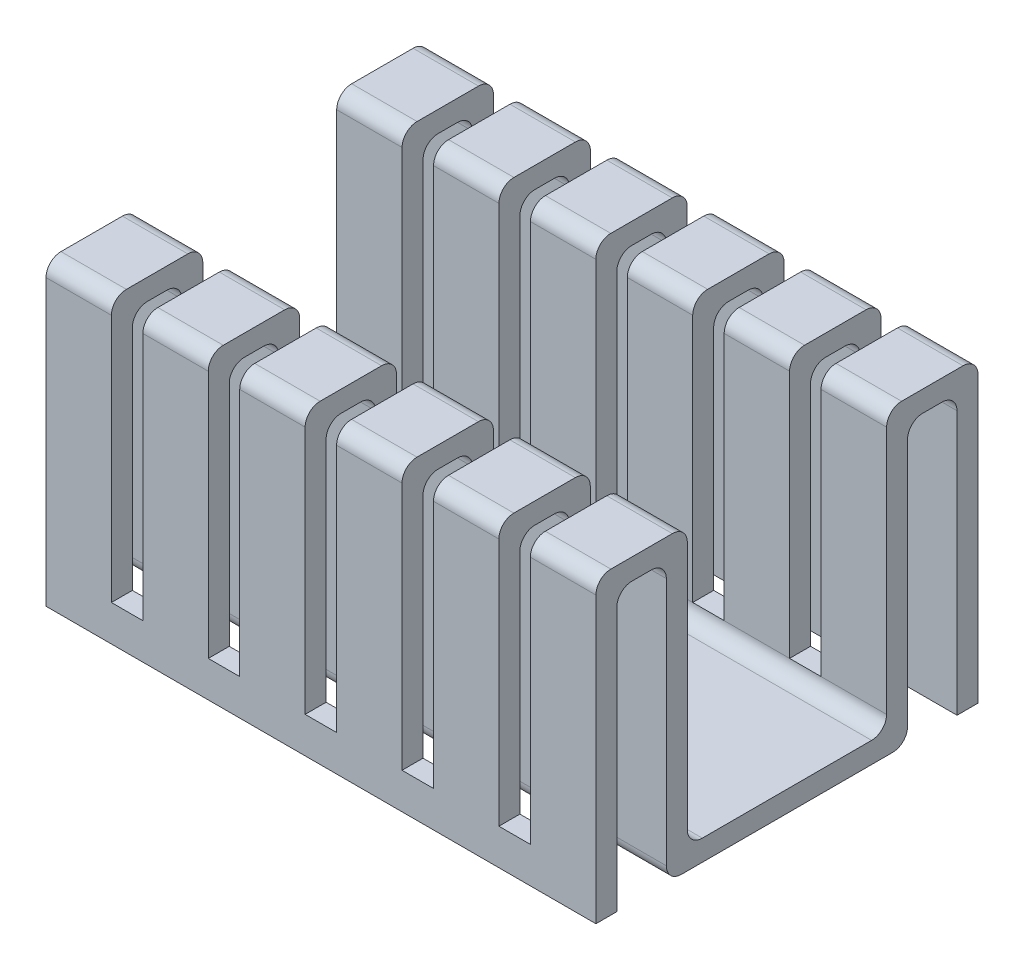
SolidWorks part; units mm, degrees
ref_plane "Front Plane" through (0, 0, 0) normal (0, 0, 1) x (1, 0, 0)
ref_plane "Top Plane" through (0, 0, 0) normal (0, 1, 0) x (1, 0, 0)
ref_plane "Right Plane" through (0, 0, 0) normal (1, 0, 0) x (0, 0, -1)
sketch "Croquis1" plane through (0, 0, 0) normal (1, 0, 0) x (0, 0, -1)
  line L5 (0, 0) -> (0, 19)
  line L9 (-1, 20) -> (-5.1, 20)
  line L10 (0, 0) -> (-1.4, 0)
  line L11 (-1.4, 0) -> (-1.4, 17.6)
  line L12 (-3.7, 18.6) -> (-2.4, 18.6)
  line L13 (-4.7, 17.6) -> (-4.7, 1)
  line L14 (-5.7, 0) -> (-19.8, 0)
  line L15 (-6.1, 2.4) -> (-6.1, 19)
  line L16 (-7.1, 1.4) -> (-18.4, 1.4)
  line L17 (-6.1, 9.3) -> (-4.7, 9.3) construction
  line L18 (-6.1, 1.4) -> (-6.1, 0) construction
  line L19 (-3.05, 20) -> (-3.05, 18.6) construction
  line L20 (-12.75, 22.5984) -> (-12.75, -4.8064) construction
  line L21 (-22.45, 20) -> (-22.45, 18.6) construction
  line L22 (-19.4, 1.4) -> (-19.4, 0) construction
  line L23 (-19.4, 9.3) -> (-20.8, 9.3) construction
  line L24 (-19.4, 2.4) -> (-19.4, 19)
  line L25 (-20.8, 17.6) -> (-20.8, 1)
  line L26 (-21.8, 18.6) -> (-23.1, 18.6)
  line L27 (-24.1, 0) -> (-24.1, 17.6)
  line L28 (-25.5, 0) -> (-24.1, 0)
  line L29 (-24.5, 20) -> (-20.4, 20)
  line L30 (-25.5, 0) -> (-25.5, 19)
  arc A0 (-20.8, 1) -> (-19.8, 0) centre (-19.8, 1) ccw
  arc A1 (-18.4, 1.4) -> (-19.4, 2.4) centre (-18.4, 2.4) cw
  arc A2 (-4.7, 1) -> (-5.7, 0) centre (-5.7, 1) cw
  arc A3 (-6.1, 2.4) -> (-7.1, 1.4) centre (-7.1, 2.4) cw
  arc A4 (-1.4, 17.6) -> (-2.4, 18.6) centre (-2.4, 17.6) ccw
  arc A5 (-3.7, 18.6) -> (-4.7, 17.6) centre (-3.7, 17.6) ccw
  arc A6 (-24.5, 20) -> (-25.5, 19) centre (-24.5, 19) ccw
  arc A7 (-23.1, 18.6) -> (-24.1, 17.6) centre (-23.1, 17.6) ccw
  arc A8 (-20.8, 17.6) -> (-21.8, 18.6) centre (-21.8, 17.6) ccw
  arc A9 (-19.4, 19) -> (-20.4, 20) centre (-20.4, 19) ccw
  arc A10 (-5.1, 20) -> (-6.1, 19) centre (-5.1, 19) ccw
  arc A11 (0, 19) -> (-1, 20) centre (-1, 19) ccw
  point P25 (-12.75, 1.4)
  point P27 (-12.75, 0)
  point P34 (-20.8, 0)
  point P40 (-4.7, 0)
  point P46 (-1.4, 18.6)
  point P49 (-4.7, 18.6)
  point P52 (-25.5, 20)
  point P55 (-24.1, 18.6)
  point P58 (-20.8, 18.6)
  point P61 (-19.4, 20)
  point P64 (-6.1, 20)
  point P67 (0, 20)
  dimension "D5" = 1
  dimension "D1" = 1.4
  dimension "D2" = 3.3
  dimension "D3" = 13.3
  dimension "D4" = 20
extrude "Saliente-Extruir1" add sketch "Croquis1" along normal blind 36.7
sketch "Croquis2" plane through (0, 1.4, 0) normal (0, 1, 0) x (1, 0, 0)
  line L0 (0, -7.625) -> (0, -17.875)
  line L1 (0, -7.1) -> (0, -18.4) construction
  line L2 (0, -17.875) -> (5.125, -17.875)
  line L3 (5.125, -17.875) -> (5.125, -7.625)
  line L4 (8.8819, -12.75) -> (-6.626, -12.75) construction
  line L5 (0, -7.625) -> (5.125, -7.625)
  line L6 (16.725, -12.75) -> (20.075, -12.75) construction
  line L7 (18.4, -14.425) -> (18.4, -11.075) construction
  circle A0 centre (18.4, -12.75) radius 1.675
  point P6 (0, -12.75)
  point P10 (5.125, -12.75)
  point P16 (18.3822, -12.1079)
  dimension "D4" = 3.35
  dimension "D1" = 5.125
  dimension "D2" = 5.125
  dimension "D3" = 11.6
extrude "Cortar-Extruir1" cut sketch "Croquis2" against normal through all
sketch "Croquis3" plane through (0, 0, 25.5) normal (0, 0, 1) x (1, 0, 0)
  line L0 (4.365, 20) -> (6.465, 20)
  line L1 (36.7, 20) -> (0, 20) construction
  line L2 (4.365, 20) -> (4.365, 2.4)
  line L3 (4.365, 2.4) -> (6.465, 2.4)
  line L4 (6.465, 2.4) -> (6.465, 20)
  line L5 (36.7, 0) -> (0, 0) construction
  line L6 (10.83, 20) -> (10.83, 2.4)
  line L7 (10.83, 20) -> (12.93, 20)
  line L8 (12.93, 2.4) -> (12.93, 20)
  line L9 (10.83, 2.4) -> (12.93, 2.4)
  line L10 (17.295, 20) -> (17.295, 2.4)
  line L11 (17.295, 20) -> (19.395, 20)
  line L12 (19.395, 2.4) -> (19.395, 20)
  line L13 (17.295, 2.4) -> (19.395, 2.4)
  line L14 (23.76, 20) -> (23.76, 2.4)
  line L15 (23.76, 20) -> (25.86, 20)
  line L16 (25.86, 2.4) -> (25.86, 20)
  line L17 (23.76, 2.4) -> (25.86, 2.4)
  line L18 (30.225, 20) -> (30.225, 2.4)
  line L19 (30.225, 20) -> (32.325, 20)
  line L20 (32.325, 2.4) -> (32.325, 20)
  line L21 (30.225, 2.4) -> (32.325, 2.4)
  line L22 (0, 20) -> (4.365, 20) construction
  line L23 (6.465, 20) -> (10.83, 20) construction
  dimension "D1" = 2.1
  dimension "D2" = 4.365
  dimension "D3" = 2.4
  dimension "D4" = 5
extrude "Cortar-Extruir2" cut sketch "Croquis3" against normal through all
